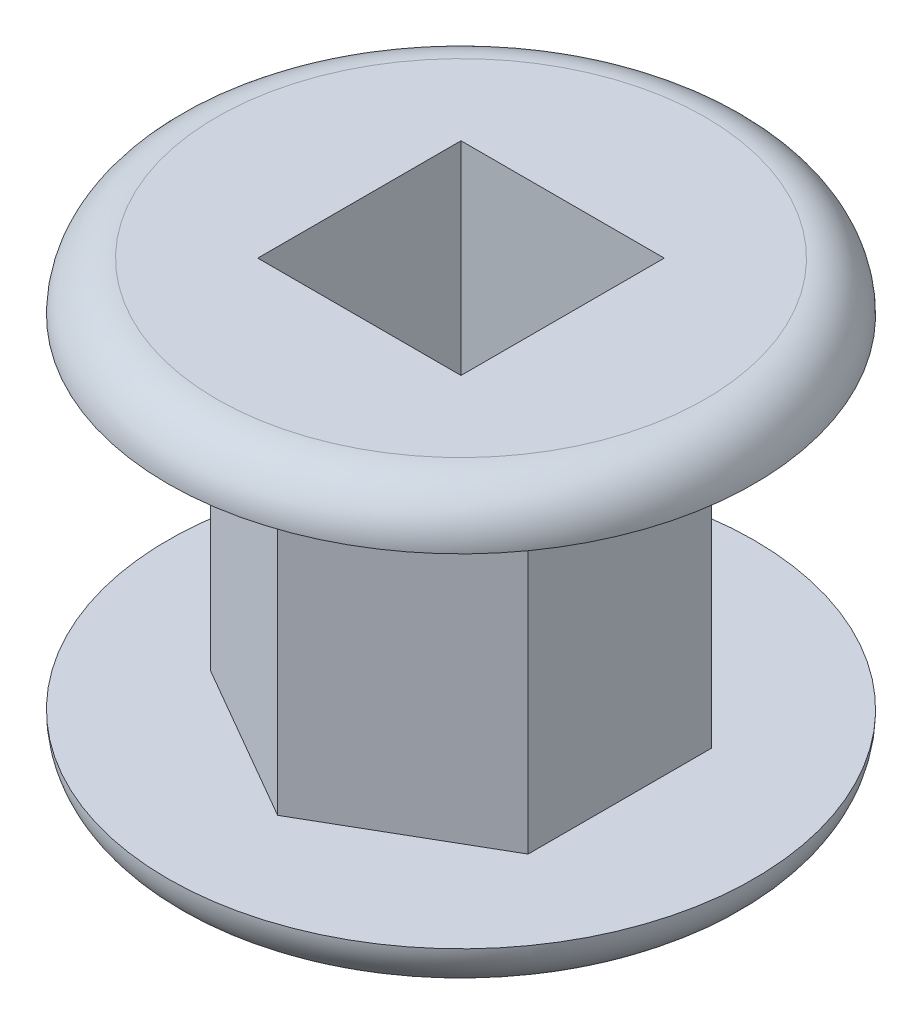
SolidWorks part; units mm, degrees
ref_plane "Front Plane" through (0, 0, 0) normal (0, 0, 1) x (1, 0, 0)
ref_plane "Top Plane" through (0, 0, 0) normal (0, 1, 0) x (1, 0, 0)
ref_plane "Right Plane" through (0, 0, 0) normal (1, 0, 0) x (0, 0, -1)
sketch "Sketch1" plane through (0, 0, 0) normal (0, 1, 0) x (1, 0, 0)
  line L1 (0, 5.9575) -> (-5.1594, 2.9788)
  line L2 (-5.1594, 2.9788) -> (-5.1594, -2.9788)
  line L3 (-5.1594, -2.9788) -> (0, -5.9575)
  line L4 (0, -5.9575) -> (5.1594, -2.9788)
  line L5 (5.1594, -2.9788) -> (5.1594, 2.9788)
  line L6 (5.1594, 2.9788) -> (0, 5.9575)
  circle A0 centre (0, 0) radius 5.1594 construction
  dimension "D1" = 10.3187
extrude "Boss-Extrude1" add sketch "Sketch1" along normal mid plane 12.7
sketch "Sketch2" plane through (0, 6.35, 0) normal (0, 1, 0) x (1, 0, 0)
  circle A0 centre (0, 0) radius 9.525
  dimension "D1" = 19.05
extrude "Boss-Extrude2" add sketch "Sketch2" along normal mid plane 1.5875
mirror "Mirror1" about plane through (0, 0, 0) normal (0, 1, 0) of "Boss-Extrude2"
sketch "Sketch3" plane through (0, 7.1437, 0) normal (0, 1, 0) x (1, 0, 0)
  line L1 (-3.302, -3.302) -> (3.302, -3.302)
  line L2 (-3.302, -3.302) -> (-3.302, 3.302)
  line L3 (-3.302, 3.302) -> (3.302, 3.302)
  line L4 (3.302, -3.302) -> (3.302, 3.302)
  line L5 (-3.302, -3.302) -> (3.302, 3.302) construction
  line L6 (-3.302, 3.302) -> (3.302, -3.302) construction
  point P0 (0, 0)
  dimension "D1" = 6.604
extrude "Cut-Extrude1" cut sketch "Sketch3" against normal through all
fillet "Fillet1" radius 1.5875 2 edges at (0, -7.1437, 9.525) (0, 7.1437, 9.525)
